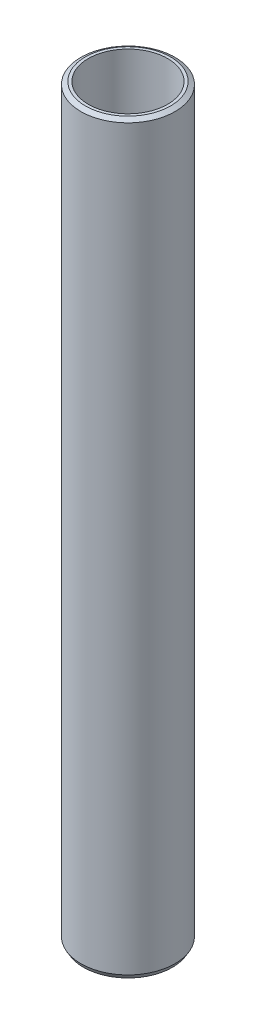
SolidWorks part; units mm, degrees
ref_plane "Front Plane" through (0, 0, 0) normal (0, 0, 1) x (1, 0, 0)
ref_plane "Top Plane" through (0, 0, 0) normal (0, 1, 0) x (1, 0, 0)
ref_plane "Right Plane" through (0, 0, 0) normal (1, 0, 0) x (0, 0, -1)
sketch "Sketch1" plane through (0, 0, 0) normal (0, 1, 0) x (1, 0, 0)
  circle A0 centre (0, 0) radius 35
  dimension "SHAFT_OD" = 70
extrude "Boss-Extrude1" add sketch "Sketch1" along normal blind 554.0188
sketch "Sketch2" plane through (0, 0, 0) normal (0, 1, 0) x (1, 0, 0)
  circle A0 centre (0, 0) radius 29.5142
  dimension "BORE_D" = 59.0284
extrude "Cut-Extrude1" cut sketch "Sketch2" along normal through all
chamfer "Chamfer1" distance 1.9356 angle 60 2 edges at (0, 554.0188, 35) (0, 0, 35) first distance on face at (0, 554.0188, 35) first distance on face at (0, 0, 29.5142)
